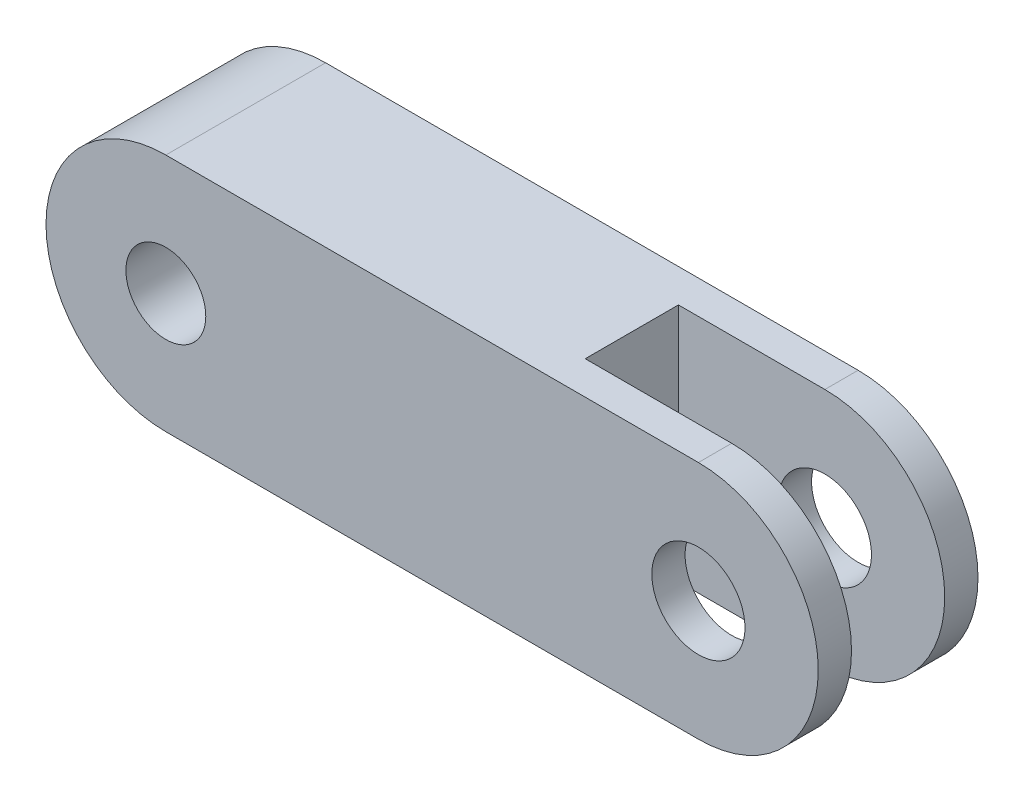
SolidWorks part; units mm, degrees
ref_plane "Front Plane" through (0, 0, 0) normal (0, 0, 1) x (1, 0, 0)
ref_plane "Top Plane" through (0, 0, 0) normal (0, 1, 0) x (1, 0, 0)
ref_plane "Right Plane" through (0, 0, 0) normal (1, 0, 0) x (0, 0, -1)
sketch "Sketch1" plane through (0, 0, 0) normal (0, 0, 1) x (1, 0, 0)
  line L0 (-10, 0) -> (10, 0) construction
  line L1 (-10, 4.5) -> (10, 4.5)
  line L2 (-10, -4.5) -> (10, -4.5)
  arc A0 (-10, 4.5) -> (-10, -4.5) centre (-10, 0) ccw
  arc A1 (10, -4.5) -> (10, 4.5) centre (10, 0) ccw
  circle A2 centre (-10, 0) radius 3.25
  circle A3 centre (10, 0) radius 1.75
  point P3 (0, 0)
  dimension "5.5" = 6.5
  dimension "D2" = 4.5
  dimension "D4" = 3.5
  dimension "D3" = 20
extrude "Boss-Extrude1" add sketch "Sketch1" along normal mid plane 6
sketch "Sketch5" plane through (0, 0, 0) normal (0, 0, 1) x (1, 0, 0)
  line L0 (10, 4.5) -> (-10, 4.5) construction
  line L1 (4.5, 4.5) -> (14.5, 4.5)
  line L2 (4.5, 4.5) -> (4.5, -4.5)
  line L3 (4.5, -4.5) -> (14.5, -4.5)
  line L4 (14.5, 4.5) -> (14.5, -4.5)
  line L5 (-10, -4.5) -> (10, -4.5) construction
  arc A0 (10, -4.5) -> (10, 4.5) centre (10, 0) ccw construction
  dimension "D1" = 10
extrude "Cut-Extrude1" cut sketch "Sketch5" against normal mid plane 3.5
sketch "Sketch6" plane through (0, 0, 3) normal (0, 0, 1) x (1, 0, 0)
  circle A0 centre (-10, 0) radius 3.25
  circle A1 centre (-10, 0) radius 3.25 construction
  circle A2 centre (-10, 0) radius 1.5
  dimension "D1" = 3
extrude "Boss-Extrude2" add sketch "Sketch6" against normal blind 4
